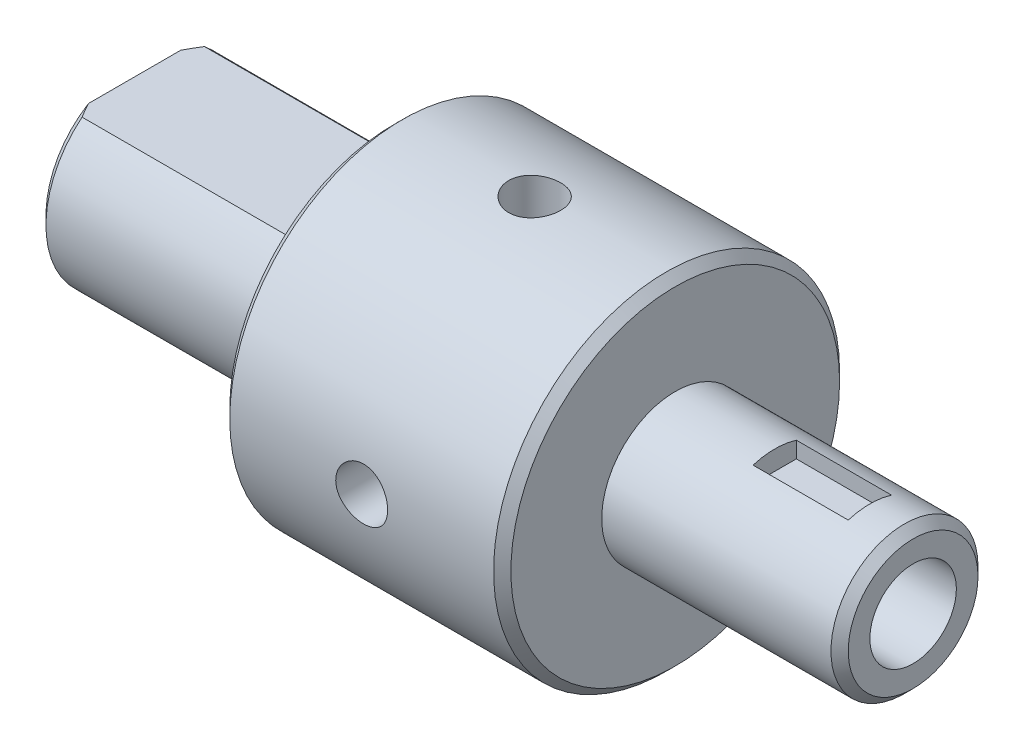
SolidWorks part; units mm, degrees
ref_plane "Спереди" through (0, 0, 0) normal (0, 0, 1) x (1, 0, 0)
ref_plane "Сверху" through (0, 0, 0) normal (0, 1, 0) x (1, 0, 0)
ref_plane "Справа" through (0, 0, 0) normal (1, 0, 0) x (0, 0, -1)
sketch "Эскиз1" plane through (0, 0, 0) normal (0, 0, 1) x (1, 0, 0)
  line L1 (0, 10) -> (0, 22.5)
  line L2 (0, 22.5) -> (60, 22.5)
  line L3 (60, 22.5) -> (60, 40)
  line L4 (60, 40) -> (125, 40)
  line L5 (125, 40) -> (125, 17)
  line L6 (125, 17) -> (180, 17)
  line L7 (180, 17) -> (180, 10)
  line L9 (0, 0) -> (-45.0163, 0) construction
  line L10 (0, 10) -> (180, 10)
  point P6 (180, 15.0333)
  dimension "D1" = 80
  dimension "D2" = 45
  dimension "D3" = 34
  dimension "D4" = 180
  dimension "D5" = 60
  dimension "D6" = 65
  dimension "D7" = 20
revolve "Повернуть1" add sketch "Эскиз1" angle 360 about L9
sketch "Эскиз6" plane through (0, 0, 0) normal (0, 0, 1) x (1, 0, 0)
  line L0 (60, 22.5) -> (0, 22.5) construction
  line L1 (148, 17) -> (170, 17)
  line L2 (148, 17) -> (148, 12.5)
  line L3 (148, 12.5) -> (170, 12.5)
  line L4 (170, 17) -> (170, 12.5)
  line L8 (180, 17) -> (125, 17) construction
  line L9 (180, -17) -> (180, 17) construction
  line L10 (0, 17.5) -> (50, 17.5)
  line L11 (0, 22.5) -> (0, -22.5) construction
  line L12 (50, 17.5) -> (50, 22.5)
  line L13 (50, 22.5) -> (0, 22.5)
  line L14 (0, 22.5) -> (0, 17.5)
  line L15 (0, -22.5) -> (60, -22.5) construction
  point P19 (0, 0)
  dimension "D1" = 22
  dimension "D2" = 10
  dimension "D3" = 4.5
  dimension "D4" = 50
  dimension "D5" = 40
extrude "Вырез-Вытянуть4" cut sketch "Эскиз6" against normal mid plane 10 contours L4 L1 L2 L3 region at (159, 14.75, 0)
extrude "Вырез-Вытянуть11" cut sketch "Эскиз6<3>" against normal through all both and the other way through all contours L13 L14 L10 L12 region at (25, 20, 0)
sketch "Эскиз6<3>" plane through (0, 0, 0) normal (0, 0, 1) x (1, 0, 0) same geometry as "Эскиз6"
sketch "Эскиз16" plane through (0, 0, 0) normal (0, 1, 0) x (1, 0, 0)
  line L0 (60, 0) -> (125, 0) construction
  line L2 (125, -17) -> (125, 17) construction
  line L3 (60, 22.5) -> (60, -22.5) construction
  circle A0 centre (92.5, 0) radius 6
  point P3 (125, 0)
  point P8 (60, 0)
  dimension "D1" = 12
  dimension "D2" = 32.5
extrude "Вырез-Вытянуть10" cut sketch "Эскиз16" against normal through all both and the other way through all
pattern_circular "Круговой массив1" count 4 over 360 about axis through (0, 0, 0) along (1, 0, 0) of "Вырез-Вытянуть10"
chamfer "Фаска3" distance 2 angle 45 4 edges at (180, 0, -17) (0, -22.5, 0) (125, 0, -40) (60, 0, -40)
